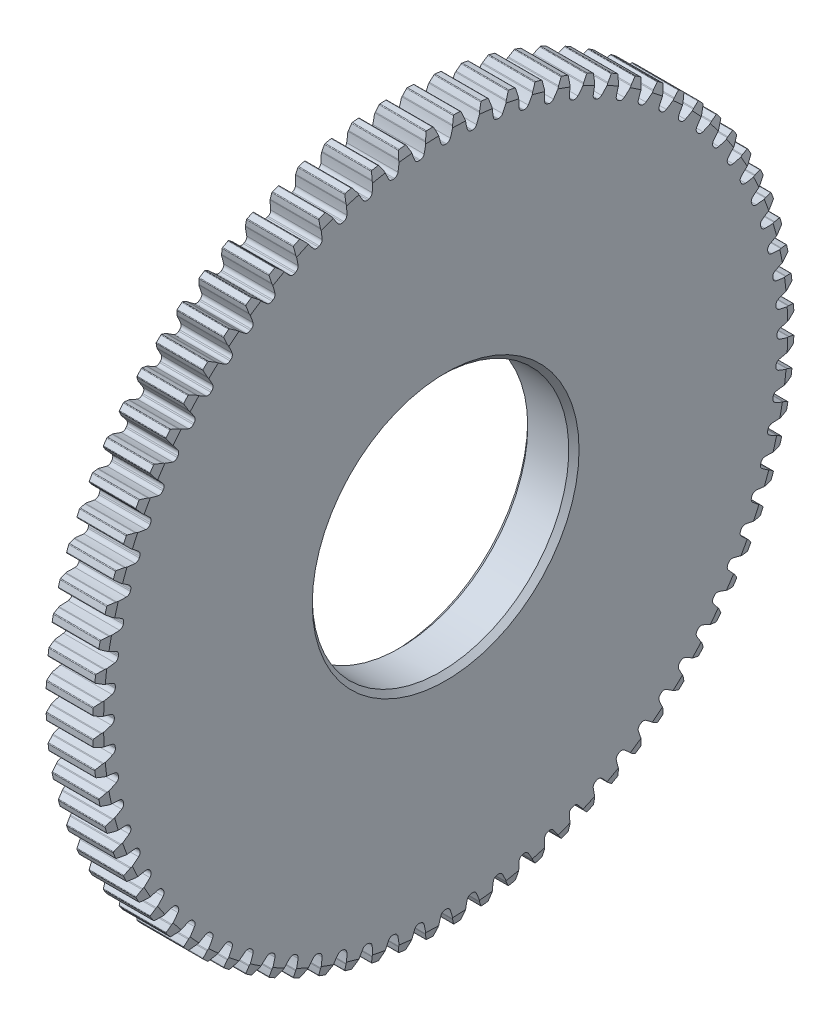
SolidWorks part; units mm, degrees
note: '?' marks a value the reader was unsure of.
material "S45C"
ref_plane "Front Plane" through (0, 0, 0) normal (0, 0, 1) x (1, 0, 0)
ref_plane "Top Plane" through (0, 0, 0) normal (0, 1, 0) x (1, 0, 0)
ref_plane "Right Plane" through (0, 0, 0) normal (1, 0, 0) x (0, 0, -1)
ref_axis "Axis_X" through (-84.99, 0, 0) along (1, 0, 0)?
ref_axis "Axis_Y" through (0, 55, 0) along (0, -1, 0)?
ref_axis "Axis_Z" through (0, 0, -88.99) along (0, 0, 1)?
sketch "Sketch1" plane through (0, 0, 0) normal (0, 0, 1) x (1, 0, 0)
  line L0 (0, 0) -> (3, 0) construction
  line L1 (0, 0) -> (0, 20)
  line L2 (0.134, 20.5) -> (2.866, 20.5)
  line L3 (3, 20) -> (3, 0)
  line L4 (2.866, 20.5) -> (3, 20)
  line L5 (0.134, 20.5) -> (0, 20)
  line L6 (3, 0) -> (0, 0)
  line L7 (0, 20) -> (3, 20) construction
  line L8 (0, 19.375) -> (3, 19.375) construction
  line L9 (0, -19.375) -> (3, -19.375) construction
  line L10 (0, -20) -> (3, -20) construction
  dimension "D_s" = 40
  dimension "G" = 38.75
  dimension "D" = 41
  dimension "B" = 3
  dimension "D1" = 15
  dimension "D2" = 0.5
revolve "Revolve1" add sketch "Sketch1" angle 360 about L0
ref_plane "Dim. W" through (3, 0, 0) normal (1, 0, 0) x (0, 0, -1)
sketch "Sketch2" plane through (0, 0, 0) normal (1, 0, 0) x (0, 0, -1)
  line L0 (0, 0) -> (0, 20.5) construction
  line L2 (0, 0) -> (0.4025, 20.496) construction
  line L6 (0.1525, 19.3744) -> (0.5841, 20.4917) construction
  line L8 (0, 0) -> (0.8048, 20.4842) construction
  circle A4 centre (0, 0) radius 19.375 construction
  circle A5 centre (0, 0) radius 20 construction
  arc A6 (0.0358, 19.375) -> (-0.0358, 19.375) centre (0, 0) ccw
  arc A7 (0.6305, 20.4903) -> (-0.6305, 20.4903) centre (0, 0) ccw
  circle A8 centre (0, 0) radius 20.5 construction
  arc A9 (0.6305, 20.4903) -> (0.5834, 20.4609) centre (0.6289, 20.4403) ccw
  arc A10 (0.2731, 19.545) -> (0.0358, 19.375) centre (0.0363, 19.625) cw
  arc A11 (0.5834, 20.4609) -> (0.4398, 20.118) centre (6.6584, 17.7153) ccw
  circle A12 centre (0.7852, 19.9846) radius 0.3703 construction
  arc A13 (0.4398, 20.118) -> (0.4252, 20.0714) centre (0.7852, 19.9846) ccw
  arc A14 (0.4252, 20.0714) -> (0.2731, 19.545) centre (-5.5571, 21.5143) cw
  arc A15 (-0.2731, 19.545) -> (-0.0358, 19.375) centre (-0.0363, 19.625) ccw
  arc A16 (-0.4252, 20.0714) -> (-0.2731, 19.545) centre (5.5571, 21.5143) ccw
  arc A17 (-0.4398, 20.118) -> (-0.4252, 20.0714) centre (-0.7852, 19.9846) cw
  arc A18 (-0.5834, 20.4609) -> (-0.4398, 20.118) centre (-6.6584, 17.7153) cw
  arc A19 (-0.6305, 20.4903) -> (-0.5834, 20.4609) centre (-0.6289, 20.4403) cw
  point P18 (0.2125, 19.3738)
  point P20 (0.3927, 19.9961)
  dimension "D4" = 0.05
  dimension "D3" = 6.6667
  dimension "D6" = 6.1538
  dimension "D7" = 0.25
  dimension "D_s" = 40
  dimension "G" = 38.75
  dimension "D5" = 2.25
  dimension "D2" = 20
  dimension "D8" = 0.425
  dimension "D1" = 1.125
extrude "Cut-Extrude1" cut sketch "Sketch2" along normal through all
pattern_circular "CirPattern1" count 80 over 360 about axis through (0, 0, 0) along (1, 0, 0) of "Cut-Extrude1"
sketch "Sketch3" [suppressed] plane through (0, 0, 0) normal (0, 0, 1) x (1, 0, 0)
  line L0 (0, 0) -> (14, 0) construction
  line L1 (14, -26.9278) -> (14, 26.9278) construction
  line L2 (14, 0) -> (8, 0)
  line L4 (14, 10.5) -> (8, 10.5)
  line L5 (8, 0) -> (8, 10.5)
  line L6 (8, 24.5) -> (8, 0) construction
  line L11 (14, 0) -> (14, 10.5)
  dimension "H" = 21
revolve "Revolve2" [suppressed] add sketch "Sketch3" angle 360 about L0
sketch "Sketch4" plane through (0, 0, 0) normal (-1, 0, 0) x (0, 0, 1)
  circle A0 centre (0, 0) radius 7.5
  dimension "P" = 15
extrude "Cut-Extrude2" cut sketch "Sketch4" against normal through all
chamfer "Chamfer1" [suppressed] distance 0.3 angle 45
chamfer "Chamfer2" [suppressed] distance 0.5 angle 45
chamfer "Chamfer3" distance 0.3 angle 45 2 edges at (3, 0, 7.5) (0, 0, 7.5)
ref_plane "Plane1" [suppressed] through (0, 10.5, 0) normal (0, 1, 0) x (1, 0, 0)
hole_wizard "Tapped Hole1" [suppressed] positions "Sketch6" profile "Sketch5" tap size "M4x0.7" standard "JIS"
sketch "Sketch6" [suppressed] plane through (-8.5, 10.5, 0) normal (0, 1, 0) x (1, 0, 0)
  line L0 (8.5, 0) -> (22.5, 0) construction
  line L7 (22.5, -26.9278) -> (22.5, 26.9278) construction
  point P0 (19.5, 0)
sketch "Sketch5" [suppressed] plane through (11, 10.5, 0) normal (1, 0, 0) x (0, 0, 1)
  line L0 (0, 0) -> (0, 21)
  line L1 (0, 21) -> (1.65, 21)
  line L2 (1.65, 21) -> (1.65, 0)
  line L5 (1.65, 0) -> (0, 0)
  line L11 (0, 0) -> (0, 21) construction
  dimension "Thru Tap Drill Dia." = 3.3
  dimension "Thru Tap Drill Depth" = 21
cosmetic thread "Hole Thread1" [suppressed] parameters "D1"=7.8562, "D2"=4
sketch "Sketch7" [suppressed] plane through (0, 0, 0) normal (1, 0, 0) x (0, 0, -1)
  line L0 (0, 5.4) -> (0, 0) construction
  line L1 (1.5, 0) -> (1.5, 5.2)
  line L2 (1.3, 5.4) -> (-1.3, 5.4)
  line L3 (-1.5, 5.2) -> (-1.5, 0)
  line L4 (-1.5, 0) -> (1.5, 0)
  circle A1 centre (0, 0) radius 4 construction
  arc A2 (1.3, 5.4) -> (1.5, 5.2) centre (1.3, 5.2) cw
  arc A3 (-1.3, 5.4) -> (-1.5, 5.2) centre (-1.3, 5.2) ccw
  point P4 (0, 4)
  point P12 (1.5, 5.4)
  dimension "D1" = 0.2
  dimension "B_s" = 3
  dimension "T_s" = 1.4
extrude "Cut-Extrude3" [suppressed] cut sketch "Sketch7" along normal through all
pattern_circular "CirPattern2" [suppressed] count 2 over 90 about axis through (-84.99, 0, 0) along (1, 0, 0)
pattern_circular "CirPattern3" [suppressed] count 2 over 120 about axis through (-84.99, 0, 0) along (1, 0, 0)
sketch "Sketch8" [suppressed] plane through (0, 0, 0) normal (0, 0, 1) x (1, 0, 0)
  line L0 (0, 0) -> (13.5, 0) construction
  line L1 (0.3, 10.5) -> (13.5, 10.5)
  line L2 (0.3, 10.5) -> (0.3, 4)
  line L3 (0.3, 4) -> (13.5, 4)
  line L4 (13.5, 10.5) -> (13.5, 4)
  line L5 (14, 10.5) -> (8, 10.5) construction
  line L6 (13.5, -10.5) -> (13.5, 10.5) construction
  line L8 (0.3, -4) -> (0.3, 3.7081) construction
  dimension "P" = 15
revolve "Revolve3" [suppressed] add sketch "Sketch8" angle 360 about L0
hole_wizard "Tapped Hole2" [suppressed] positions "Sketch10" profile "Sketch9" tap size "M3x0.5" standard "JIS"
sketch "Sketch10" [suppressed] plane through (0, 10.5, 0) normal (0, 1, 0) x (1, 0, 0)
  line L0 (0, 0) -> (14, 0) construction
  line L1 (14, -26.9278) -> (14, 26.9278) construction
  point P0 (11, 0)
sketch "Sketch9" [suppressed] plane through (11, 10.5, 0) normal (1, 0, 0) x (0, 0, 1)
  line L0 (0, 0) -> (0, 21)
  line L1 (0, 21) -> (1.25, 21)
  line L2 (1.25, 21) -> (1.25, 0)
  line L5 (1.25, 0) -> (0, 0)
  line L11 (0, 0) -> (0, 21) construction
  dimension "Thru Tap Drill Dia." = 2.5
  dimension "Thru Tap Drill Depth" = 21
cosmetic thread "Hole Thread2" [suppressed] parameters "TPC"=3
pattern_circular "CirPattern4" [suppressed] count 2 over 90 about axis through (-84.99, 0, 0) along (1, 0, 0)
pattern_circular "CirPattern5" [suppressed] count 2 over 120 about axis through (-84.99, 0, 0) along (1, 0, 0)
sketch "Sketch11" [suppressed] plane through (0, 0, 0) normal (1, 0, 0) x (0, 0, -1)
  line L0 (0, 5.4) -> (0, 0) construction
  line L1 (1.5, 0) -> (1.5, 5.2)
  line L2 (1.3, 5.4) -> (-1.3, 5.4)
  line L3 (-1.5, 5.2) -> (-1.5, 0)
  line L4 (-1.5, 0) -> (1.5, 0)
  circle A0 centre (0, 0) radius 4 construction
  arc A2 (1.3, 5.4) -> (1.5, 5.2) centre (1.3, 5.2) cw
  arc A3 (-1.3, 5.4) -> (-1.5, 5.2) centre (-1.3, 5.2) ccw
  point P4 (0, 4)
  point P12 (1.5, 5.4)
  dimension "D1" = 0.2
  dimension "B_s" = 3
  dimension "T_s" = 1.4
extrude "Cut-Extrude4" [suppressed] cut sketch "Sketch11" along normal through all
sketch "Sketch12" [suppressed] plane through (0, 0, 0) normal (0, 0, 1) x (1, 0, 0)
  line L0 (0, 0) -> (2, 0) construction
  line L3 (0, 0) -> (2, 0)
  line L4 (0, 0) -> (0, 5)
  line L5 (0, 5) -> (2, 5)
  line L6 (2, 0) -> (2, 5)
  dimension "J" = 2
  dimension "Z" = 10
revolve "Cut-Revolve1" [suppressed] cut sketch "Sketch12" angle 360 about L0
sketch "Sketch13" [suppressed] plane through (0, 0, 0) normal (0, 0, 1) x (1, 0, 0)
  line L0 (0, 0) -> (22, 0) construction
  line L2 (22, -26.9278) -> (22, 26.9278) construction
  line L3 (22, 0) -> (20, 0)
  line L4 (22, 0) -> (22, 5)
  line L5 (22, 5) -> (20, 5)
  line L6 (20, 0) -> (20, 5)
  dimension "J" = 2
  dimension "Z" = 10
revolve "Cut-Revolve2" [suppressed] cut sketch "Sketch13" angle 360 about L0
sketch "Sketch14" [suppressed] plane through (0, 0, 0) normal (0, 0, 1) x (1, 0, 0)
  line L0 (0, 0) -> (22, 0) construction
  line L2 (22, -26.9278) -> (22, 26.9278) construction
  line L3 (19, 0) -> (22, 0)
  line L4 (19, 0) -> (19, 5)
  line L5 (19, 5) -> (22, 5)
  line L6 (22, 0) -> (22, 5)
  line L7 (3, 0) -> (0, 0)
  line L8 (3, 0) -> (3, 5)
  line L9 (3, 5) -> (0, 5)
  line L10 (0, 0) -> (0, 5)
  dimension "Q" = 10
  dimension "S" = 3
  dimension "T" = 3
  dimension "R" = 10
revolve "Cut-Revolve3" [suppressed] cut sketch "Sketch14" angle 360 about L0
sketch "Sketch15" [suppressed] plane through (5.75, -2.6, 0) normal (0, 0, 1) x (1, 0, 0)
  line L0 (-5.75, 2.6) -> (-2.25, 2.6) construction
  line L1 (-3.4, 2.6) -> (-2.25, 2.6)
  line L2 (-3.4, 2.6) -> (-3.4, 8.95)
  line L3 (-3.4, 8.95) -> (-2.25, 8.95)
  line L4 (-2.25, 2.6) -> (-2.25, 8.95)
  line L7 (1.25, 2.6) -> (1.25, 8.95) construction
  dimension "D1" = 2.35
  dimension "D2_s" = 12.7
  dimension "M_s" = 1.15
  dimension "SRG" = 3.5
  dimension "J" = 7
revolve "Cut-Revolve4" [suppressed] cut sketch "Sketch15" angle 360 about L0
sketch "Sketch16" [suppressed] plane through (1.675, -2.6, 0) normal (0, 0, 1) x (1, 0, 0)
  line L0 (-1.675, 2.6) -> (17.975, 2.6) construction
  line L2 (16.825, 2.6) -> (17.975, 2.6)
  line L3 (16.825, 2.6) -> (16.825, 7.8)
  line L4 (16.825, 7.8) -> (17.975, 7.8)
  line L5 (17.975, 2.6) -> (17.975, 7.8)
  line L7 (13.325, 2.6) -> (13.325, 7.8) construction
  line L8 (20.325, -24.3278) -> (20.325, 29.5278) construction
  dimension "D1" = 2.35
  dimension "D2_s" = 10.4
  dimension "M_s" = 1.15
  dimension "SRG" = 3.5
  dimension "J" = 7
revolve "Cut-Revolve5" [suppressed] cut sketch "Sketch16" angle 360 about L0
sketch "Sketch17" [suppressed] plane through (0, 0, 0) normal (-1, 0, 0) x (0, 0, 1)
  line L0 (-8, 0) -> (8, 0) construction
  line L1 (-9.537, 9.537) -> (5.6569, -5.6569) construction
  line L2 (-8.4437, 4.875) -> (0, 0) construction
  line L3 (0, 0) -> (-4.875, 8.4437) construction
  line L4 (0, 8) -> (0, -8) construction
  circle A1 centre (-5.6569, 5.6569) radius 1.5 construction
  circle A4 centre (0, 0) radius 8 construction
  arc A5 (-6.9282, 4) -> (-4, 6.9282) centre (0, 0) cw construction
  arc A6 (-4.875, 8.4437) -> (-8.4437, 4.875) centre (0, 0) ccw
  arc A7 (-3.125, 5.4127) -> (-5.4127, 3.125) centre (0, 0) ccw
  arc A8 (-3.125, 5.4127) -> (-4.875, 8.4437) centre (-4, 6.9282) ccw
  arc A9 (-8.4437, 4.875) -> (-5.4127, 3.125) centre (-6.9282, 4) ccw
  point P22 (-5.6569, 5.6569)
  dimension "D1" = 30
  dimension "LFC" = 16
  dimension "C" = 3.5
  dimension "Angle_1" = 45
  dimension "M_1" = 3
extrude "Cut-Extrude5" [suppressed] cut sketch "Sketch17" against normal up to next
pattern_circular "CirPattern6" [suppressed] count 4 over 360 about axis through (-84.99, 0, 0) along (1, 0, 0)
sketch "Sketch18" [suppressed] plane through (0, 0, 0) normal (-1, 0, 0) x (0, 0, 1)
  line L0 (-8, 0) -> (8, 0) construction
  line L1 (-8.4437, 4.875) -> (6.9282, -4) construction
  line L2 (-9.4178, 2.5235) -> (0, 0) construction
  line L3 (0, 0) -> (-6.8943, 6.8943) construction
  line L4 (0, 8) -> (0, -8) construction
  circle A1 centre (-6.9282, 4) radius 1.5 construction
  circle A4 centre (0, 0) radius 8 construction
  arc A5 (-7.7274, 2.0706) -> (-5.6569, 5.6569) centre (0, 0) cw construction
  arc A6 (-6.8943, 6.8943) -> (-9.4178, 2.5235) centre (0, 0) ccw
  arc A7 (-4.4194, 4.4194) -> (-6.037, 1.6176) centre (0, 0) ccw
  arc A8 (-4.4194, 4.4194) -> (-6.8943, 6.8943) centre (-5.6569, 5.6569) ccw
  arc A9 (-9.4178, 2.5235) -> (-6.037, 1.6176) centre (-7.7274, 2.0706) ccw
  point P22 (-6.9282, 4)
  dimension "LTC" = 16
  dimension "D2" = 30
  dimension "C" = 3.5
  dimension "Angle_1" = 60
  dimension "M_1" = 3
extrude "Cut-Extrude6" [suppressed] cut sketch "Sketch18" against normal up to next
pattern_circular "CirPattern7" [suppressed] count 3 over 360 about axis through (-84.99, 0, 0) along (1, 0, 0)
hole_wizard "Diameter Hole1" [suppressed] positions "Sketch20" profile "Sketch19" hole size "Ø3.0" standard "JIS"
sketch "Sketch20" [suppressed] plane through (0, 0, 0) normal (-1, 0, 0) x (0, 0, 1)
  line L0 (-9.8995, 9.8995) -> (9.8995, -9.8995) construction
  line L1 (-9.8995, -9.8995) -> (9.8995, 9.8995) construction
  line L2 (0, 14) -> (0, -14) construction
  circle A0 centre (0, 0) radius 14 construction
  point P0 (-9.8995, 9.8995)
  point P10 (9.8995, -9.8995)
  point P21 (-9.8995, -9.8995)
  point P22 (9.8995, 9.8995)
  dimension "KFC" = 28
  dimension "Angle_1" = 45
sketch "Sketch19" [suppressed] plane through (0, 9.8995, -9.8995) normal (0, 1, 0) x (0, 0, 1)
  line L0 (0, 0) -> (0, 15)
  line L1 (0, 15) -> (1.5, 15)
  line L2 (1.5, 15) -> (1.5, 0)
  line L5 (1.5, 0) -> (0, 0)
  line L11 (0, 0) -> (0, 15) construction
  dimension "Thru Hole Depth" = 15
  dimension "K" = 3
hole_wizard "Diameter Hole2" [suppressed] positions "Sketch22" profile "Sketch21" hole size "Ø3.0" standard "JIS"
sketch "Sketch22" [suppressed] plane through (0, 0, 0) normal (-1, 0, 0) x (0, 0, 1)
  line L0 (0, -14) -> (0, 14) construction
  line L4 (0, 0) -> (-12.1244, 7) construction
  circle A0 centre (0, 0) radius 14 construction
  point P0 (0, -14)
  point P16 (12.1244, 7)
  point P21 (-12.1244, 7)
  dimension "KTC" = 28
  dimension "Angle_2" = 120
sketch "Sketch21" [suppressed] plane through (0, -14, 0) normal (0, 1, 0) x (0, 0, 1)
  line L0 (0, 0) -> (0, 15)
  line L1 (0, 15) -> (1.5, 15)
  line L2 (1.5, 15) -> (1.5, 0)
  line L5 (1.5, 0) -> (0, 0)
  line L11 (0, 0) -> (0, 15) construction
  dimension "Thru Hole Depth" = 15
  dimension "K" = 3
hole_wizard "Tapped Hole3" [suppressed] positions "Sketch24" profile "Sketch23" tap size "M3x0.5" standard "JIS"
sketch "Sketch24" [suppressed] plane through (0, 0, 0) normal (1, 0, 0) x (0, 0, -1)
  line L0 (0, 14) -> (0, -14) construction
  line L2 (9.8995, 9.8995) -> (0, 0) construction
  line L3 (0, 0) -> (9.8995, -9.8995) construction
  circle A0 centre (0, 0) radius 14 construction
  point P0 (9.8995, 9.8995)
  point P22 (9.8995, -9.8995)
  point P23 (-9.8995, -9.8995)
  point P24 (-9.8995, 9.8995)
  dimension "QFC" = 28
  dimension "Angle_1" = 45
  dimension "Angle_2" = 90
  dimension "Number" = 4
sketch "Sketch23" [suppressed] plane through (0, 9.8995, -9.8995) normal (0, 1, 0) x (0, 0, 1)
  line L0 (0, 0) -> (0, 7.7511)
  line L1 (0, 7.7511) -> (1.25, 7)
  line L2 (1.25, 7) -> (1.25, 0)
  line L5 (1.25, 0) -> (0, 0)
  line L10 (0, 7.7511) -> (-1.25, 7) construction
  line L11 (0, 0) -> (0, 7.7511) construction
  dimension "Tap Drill Dia." = 2.5
  dimension "Tap Drill Depth" = 7
  dimension "Drill Angle" = 118
cosmetic thread "Hole Thread3" [suppressed] parameters "Mx2"=4.5, "M"=3
cosmetic thread "Hole Thread4" [suppressed] parameters "Mx2"=4.5, "M"=3
cosmetic thread "Hole Thread5" [suppressed] parameters "Mx2"=4.5, "M"=3
cosmetic thread "Hole Thread6" [suppressed] parameters "Mx2"=4.5, "M"=3
ref_plane "Plane2" [suppressed] through (8, 0, 0) normal (1, 0, 0) x (0, 0, -1)
hole_wizard "Tapped Hole4" [suppressed] positions "Sketch26" profile "Sketch25" tap size "M3x0.5" standard "JIS"
sketch "Sketch26" [suppressed] plane through (8, 0, 0) normal (1, 0, 0) x (0, 0, -1)
  line L0 (0, -14) -> (0, 14) construction
  line L1 (0, 0) -> (9.8995, 9.8995) construction
  line L2 (0, 0) -> (9.8995, 9.8995) construction
  line L4 (0, 0) -> (9.8995, 9.8995) construction
  line L5 (0, 0) -> (9.8995, -9.8995) construction
  line L6 (-14, 0) -> (14, 0) construction
  circle A0 centre (0, 0) radius 14 construction
  point P5 (9.8995, 9.8995)
  point P24 (9.8995, -9.8995)
  point P25 (-9.8995, -9.8995)
  point P26 (-9.8995, 9.8995)
  dimension "QFC" = 28
  dimension "Angle_1" = 45
  dimension "Angle_2" = 90
  dimension "Number" = 4
sketch "Sketch25" [suppressed] plane through (8, 9.8995, -9.8995) normal (0, 1, 0) x (0, 0, -1)
  line L0 (0, 0) -> (0, 9.2511)
  line L1 (0, 9.2511) -> (1.25, 8.5)
  line L2 (1.25, 8.5) -> (1.25, 0)
  line L5 (1.25, 0) -> (0, 0)
  line L10 (0, 9.2511) -> (-1.25, 8.5) construction
  line L11 (0, 0) -> (0, 9.2511) construction
  dimension "Tap Drill Dia." = 2.5
  dimension "Tap Drill Depth" = 8.5
  dimension "Drill Angle" = 118
cosmetic thread "Hole Thread7" [suppressed] parameters "Mx2"=6, "M"=3
cosmetic thread "Hole Thread8" [suppressed] parameters "Mx2"=6, "M"=3
cosmetic thread "Hole Thread9" [suppressed] parameters "Mx2"=6, "M"=3
cosmetic thread "Hole Thread10" [suppressed] parameters "Mx2"=6, "M"=3
hole_wizard "Tapped Hole5" [suppressed] positions "Sketch28" profile "Sketch27" tap size "M3x0.5" standard "JIS"
sketch "Sketch28" [suppressed] plane through (0, 0, 0) normal (1, 0, 0) x (0, 0, -1)
  line L0 (0, 14) -> (0, -14) construction
  line L2 (12.1244, 7) -> (0, 0) construction
  circle A0 centre (0, 0) radius 14 construction
  point P0 (12.1244, 7)
  point P22 (0, -14)
  point P23 (-12.1244, 7)
  dimension "QTC" = 28
  dimension "Angle_2" = 120
  dimension "Number" = 3
sketch "Sketch27" [suppressed] plane through (0, 7, -12.1244) normal (0, 1, 0) x (0, 0, 1)
  line L0 (0, 0) -> (0, 7.7511)
  line L1 (0, 7.7511) -> (1.25, 7)
  line L2 (1.25, 7) -> (1.25, 0)
  line L5 (1.25, 0) -> (0, 0)
  line L10 (0, 7.7511) -> (-1.25, 7) construction
  line L11 (0, -6.35) -> (0, 107.95) construction
  dimension "Tap Drill Dia." = 2.5
  dimension "Tap Drill Depth" = 7
  dimension "Drill Angle" = 118
cosmetic thread "Hole Thread11" [suppressed] parameters "Mx2"=4.5, "M"=3
cosmetic thread "Hole Thread12" [suppressed] parameters "Mx2"=4.5, "M"=3
cosmetic thread "Hole Thread13" [suppressed] parameters "Mx2"=4.5, "M"=3
ref_plane "Plane3" [suppressed] through (8, 0, 0) normal (1, 0, 0) x (0, 0, -1)
hole_wizard "Tapped Hole6" [suppressed] positions "Sketch30" profile "Sketch29" tap size "M3x0.5" standard "JIS"
sketch "Sketch30" [suppressed] plane through (8, 0, 0) normal (1, 0, 0) x (0, 0, -1)
  line L0 (0, 14) -> (0, -14) construction
  line L2 (0, 0) -> (0, -14) construction
  line L3 (0, 0) -> (-12.1244, 7) construction
  circle A0 centre (0, 0) radius 14 construction
  point P0 (0, -14)
  point P20 (-12.1244, 7)
  point P21 (12.1244, 7)
  dimension "QTC" = 28
  dimension "Angle_1" = 120
  dimension "Number" = 3
sketch "Sketch29" [suppressed] plane through (8, -14, 0) normal (0, 1, 0) x (0, 0, -1)
  line L0 (0, 0) -> (0, 9.2511)
  line L1 (0, 9.2511) -> (1.25, 8.5)
  line L2 (1.25, 8.5) -> (1.25, 0)
  line L5 (1.25, 0) -> (0, 0)
  line L10 (0, 9.2511) -> (-1.25, 8.5) construction
  line L11 (0, 0) -> (0, 9.2511) construction
  dimension "Tap Drill Dia." = 2.5
  dimension "Tap Drill Depth" = 8.5
  dimension "Drill Angle" = 118
cosmetic thread "Hole Thread14" [suppressed] parameters "Mx2"=6, "M"=3
cosmetic thread "Hole Thread15" [suppressed] parameters "Mx2"=6, "M"=3
cosmetic thread "Hole Thread16" [suppressed] parameters "Mx2"=6, "M"=3
hole_wizard "CBORE for Socket Head Cap Screw1" [suppressed] positions "Sketch32" profile "Sketch31" counterbore size "M3" standard "JIS"
sketch "Sketch32" [suppressed] plane through (0, 0, 0) normal (1, 0, 0) x (0, 0, -1)
  line L0 (16, 0) -> (-16, 0) construction
  line L1 (0, -16) -> (0, 16) construction
  line L2 (11.3137, 11.3137) -> (0, 0) construction
  line L3 (0, 0) -> (11.3137, 11.3137) construction
  line L5 (0, 0) -> (11.3137, 11.3137) construction
  line L6 (0, 0) -> (11.3137, -11.3137) construction
  circle A0 centre (0, 0) radius 16 construction
  circle A1 centre (11.3137, 11.3137) radius 1.5
  point P4 (11.3137, 11.3137)
  point P25 (11.3137, -11.3137)
  point P26 (-11.3137, -11.3137)
  point P27 (-11.3137, 11.3137)
  dimension "ZFC" = 32
  dimension "U" = 3
  dimension "Angle_1" = 45
  dimension "Angle_2" = 90
  dimension "Number" = 4
sketch "Sketch31" [suppressed] plane through (0, 11.3137, -11.3137) normal (0, 1, 0) x (0, 0, 1)
  line L0 (0, 0) -> (0, 22)
  line L1 (0, 22) -> (1.75, 22)
  line L3 (1.75, 22) -> (1.75, 3.5)
  line L4 (1.75, 3.5) -> (3.25, 3.5)
  line L5 (3.25, 3.5) -> (3.25, 0)
  line L7 (3.25, 0) -> (0, 0)
  line L11 (0, 0) -> (0, 22) construction
  dimension "U2" = 3.5
  dimension "Thru Hole Depth" = 22
  dimension "U1" = 6.5
  dimension "F" = 3.5
ref_plane "Plane4" [suppressed] through (8, 0, 0) normal (1, 0, 0) x (0, 0, -1)
hole_wizard "CBORE for Socket Head Cap Screw2" [suppressed] positions "Sketch34" profile "Sketch33" counterbore size "M3" standard "JIS"
sketch "Sketch34" [suppressed] plane through (8, 0, 0) normal (1, 0, 0) x (0, 0, -1)
  line L0 (-16, 0) -> (16, 0) construction
  line L2 (0, -16) -> (0, 16) construction
  line L3 (0, 0) -> (11.3137, 11.3137) construction
  line L4 (0, 0) -> (11.3137, 11.3137) construction
  line L5 (0, 0) -> (11.3137, -11.3137) construction
  circle A0 centre (0, 0) radius 16 construction
  circle A1 centre (11.3137, 11.3137) radius 1.5
  point P0 (11.3137, 11.3137)
  point P23 (11.3137, -11.3137)
  point P24 (-11.3137, -11.3137)
  point P25 (-11.3137, 11.3137)
  dimension "Angle_1" = 45
  dimension "Angle_2" = 90
  dimension "Number" = 4
  dimension "ZFC" = 32
  dimension "U" = 3
sketch "Sketch33" [suppressed] plane through (8, 11.3137, -11.3137) normal (0, 1, 0) x (0, 0, -1)
  line L0 (0, 0) -> (0, 8)
  line L1 (0, 8) -> (1.75, 8)
  line L3 (1.75, 8) -> (1.75, 3.5)
  line L4 (1.75, 3.5) -> (3.25, 3.5)
  line L5 (3.25, 3.5) -> (3.25, 0)
  line L7 (3.25, 0) -> (0, 0)
  line L11 (0, 0) -> (0, 8) construction
  dimension "U2" = 3.5
  dimension "Thru Hole Depth" = 8
  dimension "U1" = 6.5
  dimension "F" = 3.5
hole_wizard "CBORE for Socket Head Cap Screw3" [suppressed] positions "Sketch36" profile "Sketch35" counterbore size "M3" standard "JIS"
sketch "Sketch36" [suppressed] plane through (0, 0.75, 0) normal (1, 0, 0) x (0, 0, -1)
  line L1 (0, 15.25) -> (0, -16.75) construction
  line L3 (0, -0.75) -> (0, -16.75) construction
  line L4 (0, -0.75) -> (-13.8564, 7.25) construction
  circle A0 centre (0, -0.75) radius 16 construction
  circle A1 centre (0, -16.75) radius 1.5 construction
  point P1 (0, -16.75)
  point P20 (-13.8564, 7.25)
  point P21 (13.8564, 7.25)
  dimension "ZTC" = 32
  dimension "U" = 3
  dimension "Angle_1" = 120
  dimension "Number" = 3
sketch "Sketch35" [suppressed] plane through (0, -16, 0) normal (0, 1, 0) x (0, 0, 1)
  line L0 (0, 0) -> (0, 22)
  line L1 (0, 22) -> (1.75, 22)
  line L3 (1.75, 22) -> (1.75, 3.5)
  line L4 (1.75, 3.5) -> (3.25, 3.5)
  line L5 (3.25, 3.5) -> (3.25, 0)
  line L7 (3.25, 0) -> (0, 0)
  line L11 (0, 0) -> (0, 22) construction
  dimension "U2" = 3.5
  dimension "Thru Hole Depth" = 22
  dimension "U1" = 6.5
  dimension "F" = 3.5
ref_plane "Plane5" [suppressed] through (8, 0, 0) normal (1, 0, 0) x (0, 0, -1)
hole_wizard "CBORE for Socket Head Cap Screw4" [suppressed] positions "Sketch38" profile "Sketch37" counterbore size "M3" standard "JIS"
sketch "Sketch38" [suppressed] plane through (8, 0, 0) normal (1, 0, 0) x (0, 0, -1)
  line L1 (-16, 0) -> (16, 0) construction
  line L3 (0, -16) -> (0, 16) construction
  line L5 (0, 0) -> (0, -16) construction
  line L6 (0, 0) -> (-13.8564, 8) construction
  circle A0 centre (0, 0) radius 16 construction
  circle A1 centre (0, -16) radius 1.5 construction
  point P0 (0, -16)
  point P27 (-13.8564, 8)
  point P28 (13.8564, 8)
  dimension "Angle_1" = 120
  dimension "Number" = 3
  dimension "U" = 3
  dimension "ZTC" = 32
sketch "Sketch37" [suppressed] plane through (8, -16, 0) normal (0, 1, 0) x (0, 0, -1)
  line L0 (0, 0) -> (0, 8)
  line L1 (0, 8) -> (1.75, 8)
  line L3 (1.75, 8) -> (1.75, 3.5)
  line L4 (1.75, 3.5) -> (3.25, 3.5)
  line L5 (3.25, 3.5) -> (3.25, 0)
  line L7 (3.25, 0) -> (0, 0)
  line L11 (0, 0) -> (0, 8) construction
  dimension "U2" = 3.5
  dimension "Thru Hole Depth" = 8
  dimension "U1" = 6.5
  dimension "F" = 3.5
equation "\"D4@Sketch2\"=0.1*\"Module\""
equation "\"D5@Sketch2\"=( 360 / \"Teeth@CirPattern1\" ) / 2"
equation "\"Module\"=0.5"
equation "\"Revolve2\" = if ( \"W@Dim. W\" = 0 , \"suppressed\" , \"unsuppressed\" )"
equation "\"Chamfer1\"= if ( \"W@Dim. W\" = 0 , \"suppressed\" , \"unsuppressed\" )"
equation "\"Chamfer2\" = if ( \"W@Dim. W\" = 0 , \"suppressed\" , \"unsuppressed\" )"
equation "\"Chamfer3\" = if ( \"W@Dim. W\" = 0 , \"unsuppressed\" , \"suppressed\" )"
equation "\"Plane dim\"= \"H@Sketch3\" * 0.5"
equation "\"Plane1\" = if ( \"W@Dim. W\" = 0 , \"suppressed\" , \"unsuppressed\" )"
equation "\"D1@Sketch10\" = \"W@Dim. W\" / 2"
equation "\"D1@Sketch6\" = \"W@Dim. W\" / 2"
equation "\"D1@Sketch2\"=( 360 / \"Teeth@CirPattern1\" ) / 4"
equation "\"MSM_1\"=12"
equation "\"MSM_2\"=13"
equation "\"D3@Sketch2\"=\"Teeth@CirPattern1\"/\"MSM_1\""
equation "\"D6@Sketch2\"=\"Teeth@CirPattern1\"/\"MSM_2\""
equation "\"D7@Sketch2\"=0.5*\"Module\""
equation "\"D8@Sketch2\"=0.85*\"Module\""
equation "\"Sketch3\" = if ( \"W@Dim. W\" = 0 , \"suppressed\" , \"unsuppressed\" )"
equation "\"D1@Plane2\" = iif ( \"W@Dim. W\" = 0 , \"B@Sketch1\" , iif ( \"H@Sketch3\" > = \"QFC@Sketch26\" , \"B@Sketch1\" + \"W@Dim. W\" , \"B@Sketch1\" ) )"
equation "\"D1@Plane3\" = iif ( \"W@Dim. W\" = 0 , \"B@Sketch1\" , iif ( \"H@Sketch3\" > = \"QTC@Sketch30\" , \"B@Sketch1\" + \"W@Dim. W\" , \"B@Sketch1\" ) )"
equation "\"D1@Plane4\" = iif ( \"W@Dim. W\" = 0 , \"B@Sketch1\" , iif ( \"H@Sketch3\" > = \"ZFC@Sketch34\" , \"B@Sketch1\" + \"W@Dim. W\" , \"B@Sketch1\" ) )"
equation "\"D1@Plane5\" = iif ( \"W@Dim. W\" = 0 , \"B@Sketch1\" , iif ( \"H@Sketch3\" > = \"ZTC@Sketch38\" , \"B@Sketch1\" + \"W@Dim. W\" , \"B@Sketch1\" ) )"
